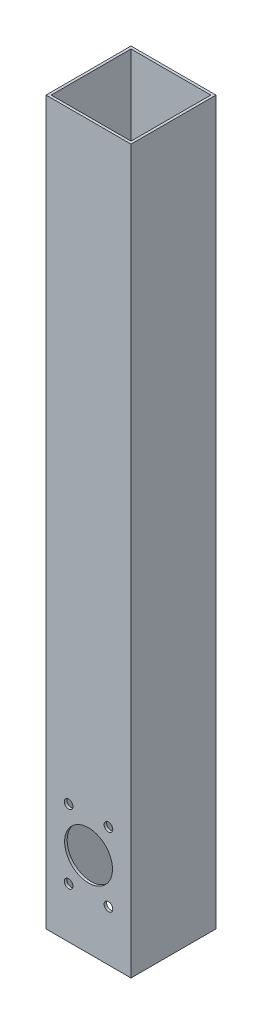
SolidWorks part; units mm, degrees
material "6061 Alloy"
ref_plane "Front Plane" through (0, 0, 0) normal (0, 0, 1) x (1, 0, 0)
ref_plane "Top Plane" through (0, 0, 0) normal (0, 1, 0) x (1, 0, 0)
ref_plane "Right Plane" through (0, 0, 0) normal (1, 0, 0) x (0, 0, -1)
sketch "Sketch1" plane through (0, 0, 0) normal (0, 1, 0) x (1, 0, 0)
  line L1 (25.4, 25.4) -> (-25.4, 25.4)
  line L2 (25.4, 25.4) -> (25.4, -25.4)
  line L3 (25.4, -25.4) -> (-25.4, -25.4)
  line L4 (-25.4, 25.4) -> (-25.4, -25.4)
  line L5 (25.4, 25.4) -> (-25.4, -25.4) construction
  line L6 (25.4, -25.4) -> (-25.4, 25.4) construction
  point P0 (0, 0)
  dimension "D1" = 50.8
extrude "Extrude-Thin1" add sketch "Sketch1" along normal blind 431.8 thin thin type one direction reverse wall 1.524
sketch "Sketch2" plane through (0, 0, 0) normal (0, 0, 1) x (1, 0, 0)
  line L0 (-36.2563, 68.2625) -> (38.5702, 68.2625) construction
  line L1 (-25.4, 0) -> (25.4, 0) construction
  line L2 (-25.4, 50.8) -> (25.4, 50.8) construction
  line L6 (25.4, 431.8) -> (25.4, 0) construction
  line L7 (-25.4, 431.8) -> (-25.4, 0) construction
  line L8 (-11.9062, 30.1778) -> (11.9063, 30.1778) construction
  line L9 (-11.9062, 71.4222) -> (11.9063, 71.4222) construction
  circle A0 centre (0, 50.8) radius 14.3002
  circle A1 centre (0, 50.8) radius 23.8125 construction
  circle A2 centre (-11.9062, 30.1778) radius 2.5908
  circle A3 centre (11.9063, 30.1778) radius 2.5908
  circle A4 centre (11.9063, 71.4222) radius 2.5908
  circle A5 centre (-11.9062, 71.4222) radius 2.5908
  point P11 (0, 50.8)
  dimension "D1" = 28.6004
  dimension "D3" = 17.4625
  dimension "D4" = 47.625
  dimension "D6" = 5.1816
  dimension "D2" = 50.8
  dimension "D5" = 60
extrude "Cut-Extrude1" cut sketch "Sketch2" along normal through all both and the other way through all
